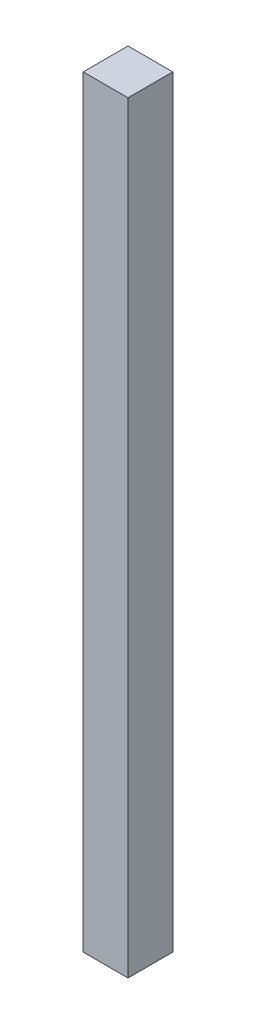
SolidWorks part; units mm, degrees
material "Concreto"
ref_plane "Plano frontal" through (0, 0, 0) normal (0, 0, 1) x (1, 0, 0)
ref_plane "Plano superior" through (0, 0, 0) normal (0, 1, 0) x (1, 0, 0)
ref_plane "Plano direito" through (0, 0, 0) normal (1, 0, 0) x (0, 0, -1)
sketch "Esboço1" plane through (0, 0, 0) normal (0, 1, 0) x (1, 0, 0)
  line L0 (50, 0) -> (-50, 0) construction
  line L1 (-50, 50) -> (50, 50)
  line L2 (-50, 50) -> (-50, -50)
  line L3 (-50, -50) -> (50, -50)
  line L4 (50, 50) -> (50, -50)
  line L5 (-50, 50) -> (50, -50) construction
  line L6 (-50, -50) -> (50, 50) construction
  point P0 (0, 0)
  dimension "D1" = 100
  dimension "D2" = 100
extrude "Ressalto-extrusão1" add sketch "Esboço1" along normal blind 1700
ref_axis "Eixo1" through (0, 0, 0) along (0, 1, 0)
